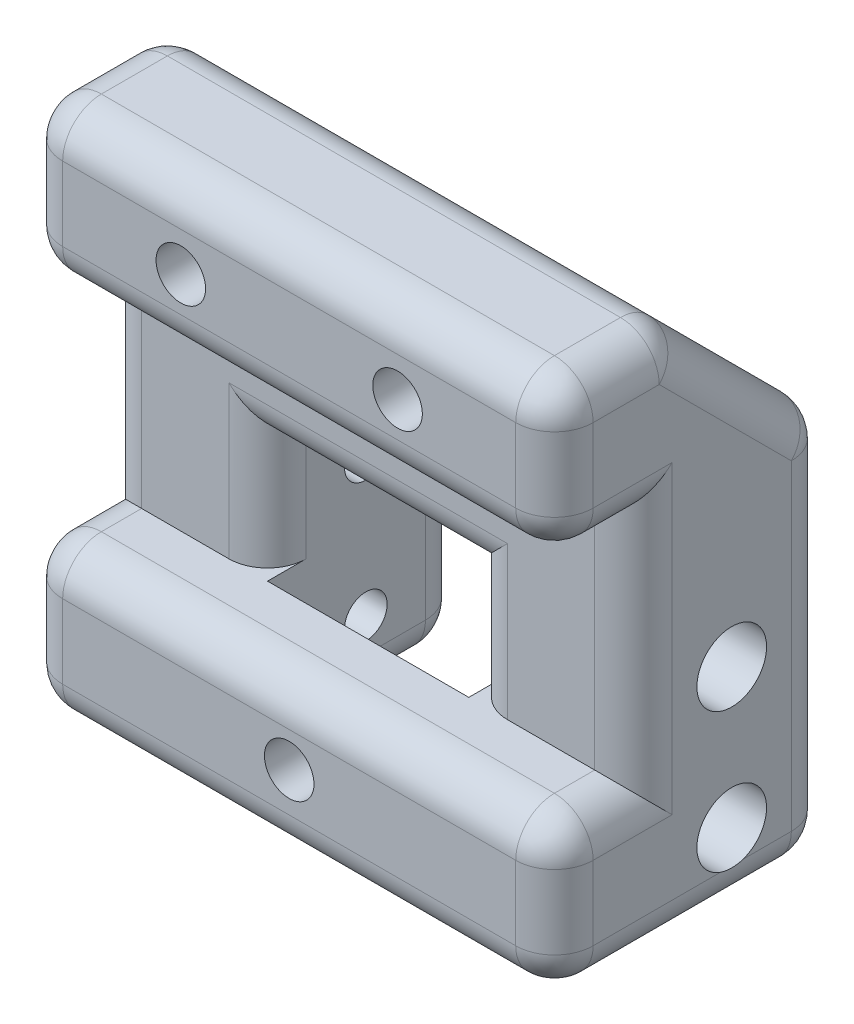
SolidWorks part; units mm, degrees
ref_plane "Front Plane" through (0, 0, 0) normal (0, 0, 1) x (1, 0, 0)
ref_plane "Top Plane" through (0, 0, 0) normal (0, 1, 0) x (1, 0, 0)
ref_plane "Right Plane" through (0, 0, 0) normal (1, 0, 0) x (0, 0, -1)
sketch "Sketch1" plane through (0, 0, 0) normal (0, 0, 1) x (1, 0, 0)
  line L1 (-34.26, 34.26) -> (34.26, 34.26)
  line L2 (-34.26, 34.26) -> (-34.26, -34.26)
  line L3 (-34.26, -34.26) -> (34.26, -34.26)
  line L4 (34.26, 34.26) -> (34.26, -34.26)
  point P4 (0, 34.26)
  point P6 (-34.26, 0)
  dimension "D1" = 68.52
extrude "Boss-Extrude1" add sketch "Sketch1" along normal blind 35.6
sketch "Sketch2" plane through (0, 0, 35.6) normal (0, 0, 1) x (1, 0, 0)
  line L0 (-34.26, 34.26) -> (-34.26, -34.26) construction
  line L1 (-34.26, -14.7) -> (34.26, -14.7)
  line L2 (-34.26, -14.7) -> (-34.26, 14.7)
  line L3 (-34.26, 14.7) -> (34.26, 14.7)
  line L4 (34.26, -14.7) -> (34.26, 14.7)
  line L5 (34.26, -34.26) -> (34.26, 34.26) construction
  point P8 (34.26, 0)
  dimension "D1" = 29.4
extrude "Cut-Extrude1" cut sketch "Sketch2" against normal blind 10.2
sketch "Sketch3" plane through (0, 0, 35.6) normal (0, 0, 1) x (1, 0, 0)
  line L0 (-14, 24.2141) -> (14, 24.2141) construction
  line L1 (0, -24.2141) -> (0, 24.2141) construction
  circle A0 centre (-14, 24.2141) radius 3.2
  circle A1 centre (14, 24.2141) radius 3.2
  circle A2 centre (0, -24.2141) radius 3.2
  point P6 (0, 24.2141)
  point P8 (0, 0)
  dimension "D2" = 6.4
  dimension "D3" = 6.4
  dimension "D4" = 6.4
  dimension "D1" = 48.4283
  dimension "D5" = 28
extrude "Cut-Extrude2" cut sketch "Sketch3" against normal blind 10.2
sketch "Sketch4" plane through (0, 0, 0) normal (0, 0, -1) x (-1, 0, 0)
  line L0 (34.26, -34.26) -> (-34.26, -34.26) construction
  line L1 (-13, -34.26) -> (13, -34.26)
  line L2 (-13, -34.26) -> (-13, 0)
  line L3 (-13, 0) -> (13, 0)
  line L4 (13, -34.26) -> (13, 0)
  point P6 (0, 0)
  dimension "D1" = 26
extrude "Cut-Extrude3" cut sketch "Sketch4" against normal blind 25.4
sketch "Sketch6" plane through (34.26, 0, 0) normal (1, 0, 0) x (0, 0, -1)
  line L0 (-25.4, 0) -> (0, 0) construction
  line L1 (-25.4, 0) -> (0, 0) construction
  circle A0 centre (-12.7, -7) radius 2.75
  circle A1 centre (-12.7, -25) radius 2.75
  point P7 (-12.7, 0)
  dimension "D2" = 5.5
  dimension "D3" = 5.5
  dimension "D1" = 7
  dimension "D4" = 25
extrude "Cut-Extrude4" cut sketch "Sketch6" against normal through all both and the other way through all
sketch "Sketch7" plane through (34.26, 0, 0) normal (1, 0, 0) x (0, 0, -1)
  circle A0 centre (-12.7, -7) radius 2.75 construction
  circle A1 centre (-12.7, -7) radius 2.75 construction
  circle A2 centre (-12.7, -7) radius 4.5
  circle A3 centre (-12.7, -25) radius 4.5
  dimension "D1" = 9
  dimension "D2" = 9
extrude "Cut-Extrude5" cut sketch "Sketch7" against normal offset from surface (13.26 mm away) 8 up to face at (13, -4.25, 12.7)
sketch "Sketch8" plane through (-34.26, 0, 0) normal (-1, 0, 0) x (0, 0, 1)
  circle A0 centre (12.7, -7) radius 4.5
  circle A1 centre (12.7, -25) radius 4.5
  dimension "D1" = 9
  dimension "D2" = 9
extrude "Cut-Extrude6" cut sketch "Sketch8" against normal offset from surface (13.26 mm away) 8 up to face at (-13, -9.75, 12.7)
chamfer "Chamfer1" distance 20 angle 45 1 edges at (0, 34.26, 0)
fillet "Fillet2" radius 5 35 edges at (-34.26, -34.26, 17.8) (34.26, -34.26, 17.8) (-34.26, -14.7, 30.5) (34.26, -14.7, 30.5) (34.26, -10, 0) (34.26, 24.26, 10) (34.26, 34.26, 27.8) (-34.26, -10, 0) (-34.26, 24.26, 10) (-34.26, 34.26, 27.8) (34.26, 14.7, 30.5) (-34.26, 14.7, 30.5) (0, 0, 25.4) (23.63, -34.26, 0) (13, -34.26, 12.7) (-13, -34.26, 12.7) (0, -34.26, 25.4) (-23.63, -34.26, 0) (13, -17.13, 0) (-13, -17.13, 0) (0, -34.26, 35.6) (0, -14.7, 35.6) (34.26, 0, 25.4) (0, 34.26, 35.6) (0, 14.7, 35.6) (-34.26, 0, 25.4) (34.26, 24.48, 35.6) (-34.26, 24.48, 35.6) (34.26, -24.48, 35.6) (-34.26, -24.48, 35.6) (0, 0, 0) (0, 14.26, 0) (0, 34.26, 20) (-13, -7.35, 25.4) (13, -7.35, 25.4)
